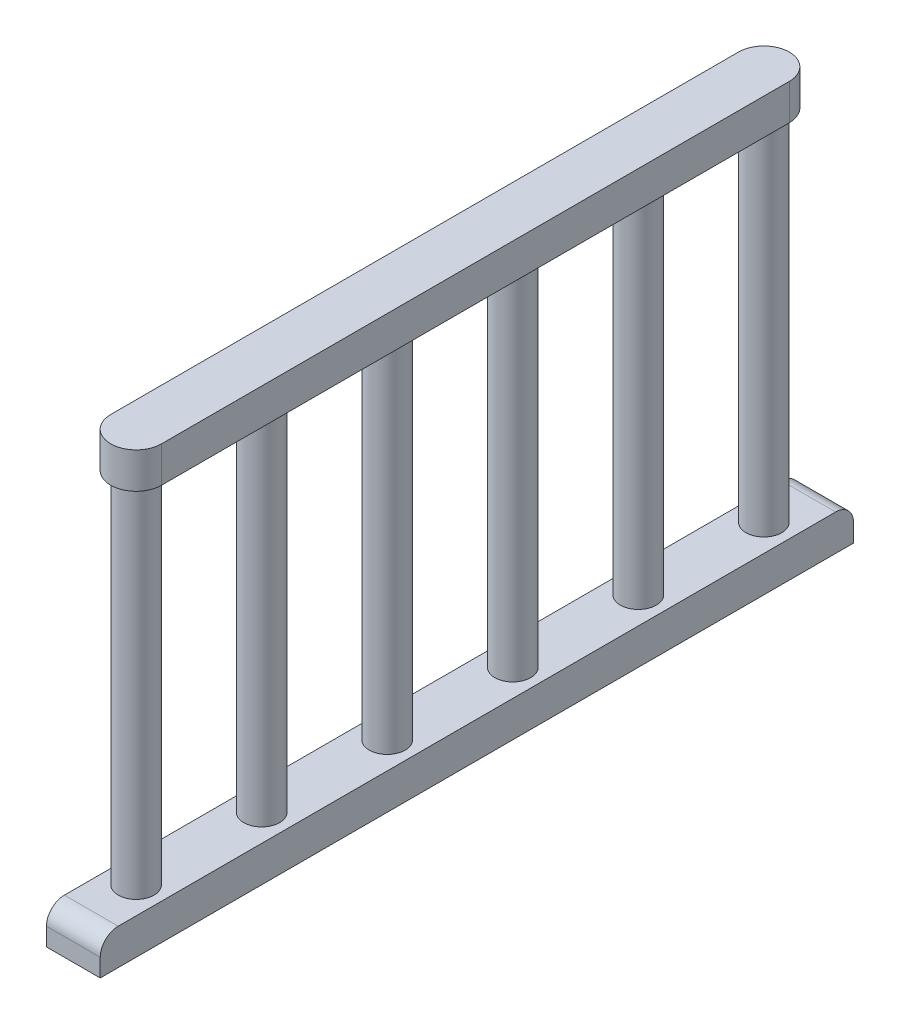
SolidWorks part; units mm, degrees
material "Alloy Steel"
ref_plane "Front Plane" through (0, 0, 0) normal (0, 0, 1) x (1, 0, 0)
ref_plane "Top Plane" through (0, 0, 0) normal (0, 1, 0) x (1, 0, 0)
ref_plane "Right Plane" through (0, 0, 0) normal (1, 0, 0) x (0, 0, -1)
sketch "Sketch2" plane through (0, 0, 0) normal (0, 1, 0) x (1, 0, 0)
  line L0 (0, -12.024) -> (0, 987.976) construction
  line L1 (-1850, -12.024) -> (1850, -12.024) construction
  line L2 (1850, -12.024) -> (1700, -12.024)
  line L3 (-1850, -12.024) -> (-1700, -12.024)
  line L4 (-1850, -12.024) -> (-1850, 2087.976)
  line L5 (-1850, 2087.976) -> (-1700, 2087.976)
  line L6 (-1700, -12.024) -> (-1700, 2087.976)
  line L7 (1850, 2087.976) -> (1700, 2087.976)
  line L8 (1850, -12.024) -> (1850, 2087.976)
  line L9 (1700, -12.024) -> (1700, 2087.976)
  dimension "D1" = 1000
  dimension "D2" = 1850
  dimension "D3" = 2100
  dimension "D4" = 150
extrude "Boss-Extrude3" add sketch "Sketch2" along normal blind 100
ref_plane "Plane1" through (0, 100, 0) normal (0, 1, 0) x (1, 0, 0)
sketch "Sketch3" plane through (0, 100, 0) normal (0, 1, 0) x (1, 0, 0)
  line L0 (0, 0) -> (0, 2142.9852) construction
  line L1 (-1775, -12.024) -> (-1775, 162.976) construction
  line L2 (-1850, -12.024) -> (-1700, -12.024) construction
  circle A0 centre (-1775, 162.976) radius 50
  dimension "D2" = 100
  dimension "D1" = 175
extrude "Boss-Extrude4" add sketch "Sketch3" along normal blind 1000
pattern_linear "LPattern1" count 6 spacing 350 along (0, 0, -1) of "Boss-Extrude4"
sketch "Sketch5" plane through (0, 100, 0) normal (0, 1, 0) x (1, 0, 0)
  line L0 (1775, 2087.976) -> (1775, 1912.976) construction
  line L1 (1850, 2087.976) -> (1700, 2087.976) construction
  circle A0 centre (1775, 1912.976) radius 50
  dimension "D2" = 100
  dimension "D1" = 175
extrude "Boss-Extrude5" add sketch "Sketch5" along normal blind 1000
pattern_linear "LPattern2" count 6 spacing 350 along (0, 0, 1) of "Boss-Extrude5"
ref_plane "Plane3" through (0, 1100, 0) normal (0, 1, 0) x (1, 0, 0)
fillet "Fillet1" radius 50 1 edges at (-1775, 100, -2087.976)
fillet "Fillet2" radius 50 1 edges at (-1775, 100, 12.024)
fillet "Fillet3" radius 50 1 edges at (1775, 100, 12.024)
fillet "Fillet4" radius 50 1 edges at (1775, 100, -2087.976)
sketch "Sketch13" plane through (0, 1100, 0) normal (0, 1, 0) x (1, 0, 0)
  line L0 (-1775, 162.976) -> (-1775, 1912.976) construction
  line L1 (-1845.8383, 162.976) -> (-1845.8383, 1912.976)
  line L2 (-1704.1617, 162.976) -> (-1704.1617, 1912.976)
  line L3 (0, 0) -> (0, 2341.2867) construction
  line L4 (0, -605) -> (0, 605) construction
  line L5 (1775, 162.976) -> (1775, 1912.976) construction
  line L6 (1845.8383, 162.976) -> (1845.8383, 1912.976)
  line L7 (1704.1617, 162.976) -> (1704.1617, 1912.976)
  arc A0 (-1845.8383, 162.976) -> (-1704.1617, 162.976) centre (-1775, 162.976) ccw
  arc A1 (-1704.1617, 1912.976) -> (-1845.8383, 1912.976) centre (-1775, 1912.976) ccw
  arc A2 (1845.8383, 162.976) -> (1704.1617, 162.976) centre (1775, 162.976) cw
  arc A3 (1704.1617, 1912.976) -> (1845.8383, 1912.976) centre (1775, 1912.976) cw
  point P4 (-1775, 1037.976)
  point P16 (1775, 1037.976)
extrude "Boss-Extrude8" add sketch "Sketch13" along normal blind 100
sketch "Sketch14" plane through (0, 1100, 0) normal (0, 1, 0) x (1, 0, 0)
  line L1 (-1899.1526, 2186.8784) -> (-1093.8951, 2186.8784)
  line L2 (-1899.1526, 2186.8784) -> (-1899.1526, -316.0877)
  line L3 (-1899.1526, -316.0877) -> (-1093.8951, -316.0877)
  line L4 (-1093.8951, 2186.8784) -> (-1093.8951, -316.0877)
extrude "Cut-Extrude1" cut sketch "Sketch14" against normal blind 2000 and the other way blind 2000
